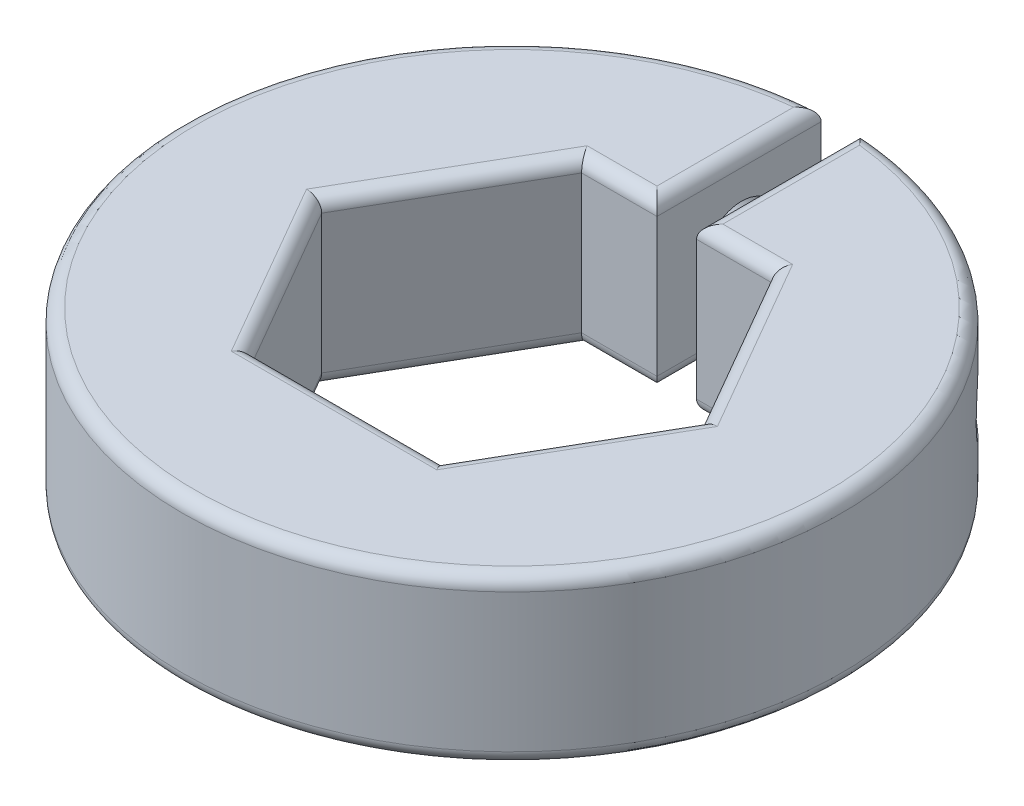
SolidWorks part; units mm, degrees
ref_plane "Front" through (0, 0, 0) normal (0, 0, 1) x (1, 0, 0)
ref_plane "Top" through (0, 0, 0) normal (0, 1, 0) x (1, 0, 0)
ref_plane "Right" through (0, 0, 0) normal (1, 0, 0) x (0, 0, -1)
sketch "Sketch1" plane through (0, 0, 0) normal (0, 1, 0) x (1, 0, 0)
  line L1 (7.3323, 0) -> (3.6662, 6.35)
  line L2 (3.6662, 6.35) -> (-3.6662, 6.35)
  line L3 (-3.6662, 6.35) -> (-7.3323, 0)
  line L4 (-7.3323, 0) -> (-3.6662, -6.35)
  line L5 (-3.6662, -6.35) -> (3.6662, -6.35)
  line L6 (3.6662, -6.35) -> (7.3323, 0)
  circle A0 centre (0, 0) radius 6.35 construction
  circle A1 centre (0, 0) radius 12.7
  dimension "D1" = 25.4
extrude "Boss-Extrude1" add sketch "Sketch1" along normal blind 6.35
sketch "Sketch2" plane through (0, 0, 0) normal (1, 0, 0) x (0, 0, -1)
  line L1 (2.5825, 11.4433) -> (19.1044, 11.4433)
  line L2 (2.5825, 11.4433) -> (2.5825, -4.621)
  line L3 (2.5825, -4.621) -> (19.1044, -4.621)
  line L4 (19.1044, 11.4433) -> (19.1044, -4.621)
  line L5 (2.5825, 11.4433) -> (19.1044, -4.621) construction
  line L6 (2.5825, -4.621) -> (19.1044, 11.4433) construction
  point P4 (10.8435, 3.4112)
extrude "Cut-Extrude1" cut sketch "Sketch2" against normal blind 0.762 and the other way blind 0.762
sketch "Sketch3" plane through (0.762, 0, 0) normal (-1, 0, 0) x (0, 0, 1)
  line L0 (-6.35, 0) -> (-12.6771, 6.35) construction
  circle A0 centre (-9.6098, 3.2716) radius 1.45
extrude "Cut-Extrude2" cut sketch "Sketch3" against normal through all and the other way through all
fillet "Fillet1" radius 0.508 20 edges at (5.4993, 0, -3.175) (5.4993, 0, 3.175) (0, 0, 6.35) (-5.4993, 0, 3.175) (-5.4993, 0, -3.175) (-2.2141, 0, -6.35) (-0.762, 0, -9.5136) (0, 0, 12.7) (0.762, 0, -9.5136) (2.2141, 0, -6.35) (0, 6.35, 12.7) (-0.762, 6.35, -9.5136) (-2.2141, 6.35, -6.35) (-5.4993, 6.35, -3.175) (-5.4993, 6.35, 3.175) (0, 6.35, 6.35) (5.4993, 6.35, 3.175) (5.4993, 6.35, -3.175) (2.2141, 6.35, -6.35) (0.762, 6.35, -9.5136)
